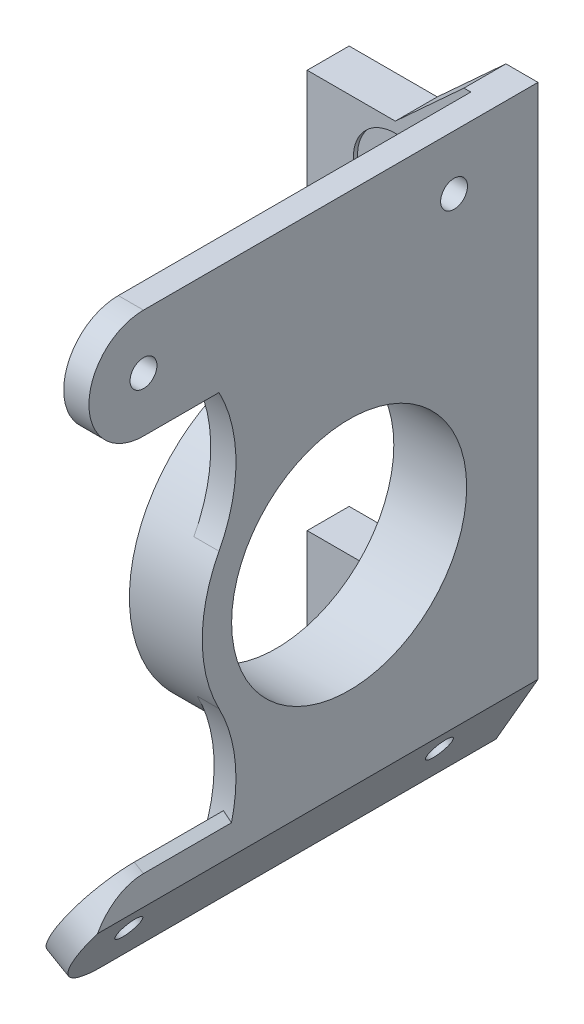
SolidWorks part; units mm, degrees
ref_plane "前视基准面" through (0, 0, 0) normal (0, 0, 1) x (1, 0, 0)
ref_plane "上视基准面" through (0, 0, 0) normal (0, 1, 0) x (1, 0, 0)
ref_plane "右视基准面" through (0, 0, 0) normal (1, 0, 0) x (0, 0, -1)
sketch "草图2" plane through (0, 0, 0) normal (0, 0, 1) x (1, 0, 0)
  line L0 (-14.7736, 24.3382) -> (-14.7736, -35.6618)
  line L1 (-14.7736, -35.6618) -> (30.2264, -35.6618)
  line L2 (7.7264, -35.6618) -> (7.7264, -23.1618)
  line L3 (21.55, -23.1618) -> (-6.0971, -23.1618)
  line L4 (-6.0971, -23.1618) -> (-6.0971, 11.8382)
  line L5 (-6.0971, 11.8382) -> (21.55, 11.8382)
  line L6 (7.7264, 11.8382) -> (7.7264, 24.3382)
  line L7 (30.2264, 24.3382) -> (-14.7736, 24.3382)
  line L8 (7.7264, 28.8603) -> (7.7264, -39.8897) construction
  line L9 (21.55, -23.1618) -> (21.55, 11.8382)
  line L10 (30.2264, 24.3382) -> (30.2264, -35.6618)
  line L11 (-18.1559, -5.6618) -> (33.2411, -5.6618) construction
  point P16 (-6.0971, -5.6618)
  point P17 (-14.7736, -5.6618)
  dimension "D1" = 45
  dimension "D2" = 35
  dimension "D3" = 60
extrude "凸台-拉伸2" add sketch "草图2" along normal blind 5 contours L6 L7 L0 L1 L2 L3 L4 L5 | L10 L7 L6 L5 L9 L3 L2 L1 region at (-3.5236, 23.6974, 0) region at (18.9764, 23.6974, 0)
sketch "草图4" plane through (0, 0, 5) normal (0, 0, 1) x (1, 0, 0)
  line L0 (-18.165, -5.6618) -> (33.9165, -5.6618) construction
  line L1 (-14.7736, 24.3382) -> (-14.7736, -35.6618) construction
  line L2 (-14.7736, -23.1618) -> (-6.0971, -23.1618)
  line L3 (-14.7736, -23.1618) -> (-14.7736, 11.8382)
  line L4 (-14.7736, 11.8382) -> (-6.0971, 11.8382)
  line L5 (-6.0971, -23.1618) -> (-6.0971, 11.8382)
  line L6 (-6.0971, -23.1618) -> (-6.0971, 11.8382) construction
  line L7 (7.7264, -39.813) -> (7.7264, 28.1228) construction
  line L8 (30.2264, 11.8382) -> (21.55, 11.8382)
  line L9 (21.55, -23.1618) -> (21.55, 11.8382)
  line L10 (30.2264, -23.1618) -> (21.55, -23.1618)
  line L11 (30.2264, -23.1618) -> (30.2264, 11.8382)
  point P17 (-14.7736, -5.6618)
  dimension "D1" = 35
extrude "凸台-拉伸15" add sketch "草图4" along normal blind 35
sketch "草图5" plane through (-14.7736, 0, 0) normal (-1, 0, 0) x (0, 0, 1)
  line L0 (0, -5.6618) -> (40, -5.6618)
  line L1 (0, 24.3382) -> (0, -35.6618) construction
  line L2 (40, 11.8382) -> (40, -23.1618) construction
  line L3 (22.5, 11.8382) -> (40, 11.8382)
  line L4 (40, 11.8382) -> (40, -23.1618)
  line L5 (40, -23.1618) -> (22.5, -23.1618)
  circle A0 centre (22.5, -5.6618) radius 17.5
  line M5 (5, -23.1618) -> (40, -23.1618)
  line M6 (40, -23.1618) -> (40, 11.8382)
  line M7 (40, 11.8382) -> (5, 11.8382)
  dimension "D1" = 35
extrude "切除-拉伸1" cut sketch "草图5" against normal blind 45 contours A0 M5 M6 | A0 M6 M7 region at (-14.7736, 7.9293, 36.0911) region at (-14.7736, -19.2528, 36.0911)
sketch "草图6" plane through (-14.7736, 0, 0) normal (-1, 0, 0) x (0, 0, 1)
  circle A0 centre (22.5, -5.6618) radius 14
  dimension "D1" = 28
extrude "切除-拉伸2" cut sketch "草图6" against normal blind 45
fillet "圆角1" radius 5 4 edges at (-6.0971, 11.8382, 2.5) (21.55, 11.8382, 2.5) (-6.0971, -23.1618, 2.5) (21.55, -23.1618, 2.5)
sketch "草图7" plane through (-6.0971, 0, 0) normal (1, 0, 0) x (0, 0, -1)
  circle A0 centre (-22.5, -5.6618) radius 15
  circle A1 centre (-22.5, -5.6618) radius 13
extrude "凸台-拉伸16" add sketch "草图7" against normal blind 1
sketch "草图8" plane through (21.55, 0, 0) normal (-1, 0, 0) x (0, 0, 1)
  circle A0 centre (22.5, -5.6618) radius 15
  circle A1 centre (22.5, -5.6618) radius 10
sketch "草图9" plane through (0, 0, 5) normal (0, 0, 1) x (1, 0, 0)
  line L0 (7.7264, 24.3382) -> (7.7264, -35.6618)
  line L13 (30.2264, 24.3382) -> (-14.7736, 24.3382) construction
  line L14 (-14.7736, -35.6618) -> (30.2264, -35.6618) construction
sketch "草图11" plane through (0, 0, 5) normal (0, 0, 1) x (1, 0, 0)
  line L0 (-14.7736, 18.0882) -> (30.2264, 18.0882)
  line L1 (-14.7736, 24.3382) -> (-14.7736, 11.8382) construction
  line L2 (30.2264, 24.3382) -> (30.2264, 11.8382) construction
  line L3 (7.7264, 24.3382) -> (7.7264, -35.6618) construction
  line L4 (30.2264, 24.3382) -> (-14.7736, 24.3382) construction
  line L5 (-14.7736, -35.6618) -> (30.2264, -35.6618) construction
  line L6 (7.7264, -5.6618) -> (45.6912, -5.6618) construction
  line L7 (45.6912, -5.6618) -> (45.6912, 4.9969) construction
  line L10 (-14.7736, -29.4118) -> (30.2264, -29.4118)
  line L11 (-14.7736, -23.1618) -> (-14.7736, -35.6618) construction
  point P4 (-2.7736, 18.0882)
  point P16 (-2.7736, -29.4118)
  point P18 (18.2264, -29.4118)
  point P25 (18.2264, 18.0882)
  dimension "D1" = 12
split "分割1" trim tools "草图9" bodies to split 111 resulting bodies 117 118
delete or keep bodies "实体-删除/保留 2" type delete bodies bodies 117
hole_wizard "打孔尺寸(%根据六角头螺)栓 全螺纹的类型1" positions "3D草图2" profile "草图31" counterbore size "M4" standard "GB"
sketch3d "3D草图2"
  point P0 (18.2264, 18.0882, 5)
  point P3 (18.2264, -29.4118, 5)
sketch "草图31" plane through (18.2264, 18.0882, 5) normal (1, 0, 0) x (0, -1, 0)
  line L0 (0, 0) -> (0, 6.2919)
  line L1 (0, 6.2919) -> (2.15, 5)
  line L2 (2.15, 5) -> (2.15, 0.5)
  line L3 (2.15, 0.5) -> (5, 0.5)
  line L4 (5, 0.5) -> (5, 0)
  line L5 (5, 0) -> (0, 0)
  line L10 (0, 6.2919) -> (-2.15, 5) construction
  line L11 (0, -6.35) -> (0, 107.95) construction
  dimension "孔直径" = 4.3
  dimension "孔深度" = 5
  dimension "柱形沉头孔直径" = 10
  dimension "柱形沉头孔深度" = 0.5
  dimension "导头角度" = 118
sketch "草图17" plane through (0, 0, 5) normal (0, 0, 1) x (1, 0, 0)
  line L5 (30.2264, 31.8382) -> (27.2264, 31.8382)
  line L6 (30.2264, 31.8382) -> (30.2264, 18.8382)
  line L7 (30.2264, 18.8382) -> (27.2264, 18.8382)
  line L8 (27.2264, 31.8382) -> (27.2264, 18.8382)
  line L9 (30.2264, 24.3382) -> (30.2264, 11.8382) construction
  line L10 (30.2264, 11.8382) -> (21.55, 11.8382) construction
  dimension "D1" = 3
  dimension "D4" = 13
  dimension "D6" = 7
extrude "凸台-拉伸20" add sketch "草图17" along normal blind 42
sketch "草图18" plane through (30.2264, 0, 0) normal (1, 0, 0) x (0, 0, -1)
  line L3 (-47, 18.8382) -> (-47, 31.8382)
  arc A0 (-47, 31.8382) -> (-47, 18.8382) centre (-47, 25.3382) ccw
extrude "凸台-拉伸21" add sketch "草图18" against normal blind 3
sketch "草图19" plane through (30.2264, 0, 0) normal (1, 0, 0) x (0, 0, -1)
  circle A0 centre (-47, 25.3382) radius 1.6
  circle A2 centre (-10, 25.3382) radius 1.6
  dimension "D1" = 37
extrude "切除-拉伸3" cut sketch "草图19" against normal blind 3
sketch "草图24" plane through (30.2264, 0, 0) normal (1, 0, 0) x (0, 0, -1)
  line L11 (-5, 18.8382) -> (-38, 18.8382)
  line L12 (-5, 18.8382) -> (-5, 11.8382)
  line L14 (-38, 18.8382) -> (-38, 2.4623) construction
  line L15 (-22.5, 11.8382) -> (-5, 11.8382) construction
  line L16 (-22.5, 11.8382) -> (-5, 11.8382)
  line L19 (-5, 11.8382) -> (-5, -23.1618) construction
  line L21 (-38, 2.4623) -> (-38, -13.7858) construction
  arc A2 (-22.5, 11.8382) -> (-22.5, -23.1618) centre (-22.5, -5.6618) ccw construction
  arc A3 (-22.5, 11.8382) -> (-38, 2.4623) centre (-22.5, -5.6618) ccw
  arc A4 (-38, 2.4623) -> (-38, -13.7858) centre (-22.5, -5.6618) ccw construction
  arc A6 (-38, 2.4623) -> (-38, 18.8382) centre (-53.622, 10.6503) ccw
  dimension "D1" = 33
extrude "凸台-拉伸25" add sketch "草图24" against normal blind 3
sketch "草图21" plane through (0, 0, 5) normal (0, 0, 1) x (1, 0, 0)
  line L1 (30.2264, 18.8382) -> (30.2264, 31.8382) construction
  line L5 (18.2264, 24.3382) -> (30.2264, 24.3382)
  line L6 (27.2264, 24.3382) -> (7.7264, 24.3382) construction
  line L8 (30.2264, 24.3382) -> (30.2264, 31.8382)
  line L9 (26.4082, 31.8382) -> (18.2264, 24.3382)
  line L15 (30.2264, 31.8382) -> (26.4082, 31.8382)
  line L16 (30.2264, 31.8382) -> (30.2264, 35.3382) construction
  line L17 (30.2264, 35.3382) -> (26.4082, 31.8382) construction
  dimension "D3" = 12
  dimension "D4" = 11
extrude "凸台-拉伸22" add sketch "草图21" against normal blind 5
sketch "草图34" plane through (0, 0, 5) normal (0, 0, 1) x (1, 0, 0)
  line L0 (30.2264, -23.1618) -> (30.2264, -35.6618) construction
  line L1 (22.6283, -36.9201) -> (25.2264, -38.4201)
  line L2 (22.6283, -36.9201) -> (29.1283, -25.6618)
  line L3 (29.1283, -25.6618) -> (30.2264, -26.2957)
  line L4 (25.2264, -38.4201) -> (30.2264, -29.7598)
  line L5 (22.6283, -36.9201) -> (31.7264, -27.1618) construction
  line L6 (29.1283, -25.6618) -> (25.2264, -38.4201) construction
  line L7 (21.55, -23.1618) -> (30.2264, -23.1618) construction
  line L8 (30.2264, -26.2957) -> (30.2264, -29.7598)
  line L9 (30.2264, -29.7598) -> (31.7264, -27.1618) construction
  line L10 (30.2264, -26.2957) -> (31.7264, -27.1618) construction
  point P0 (27.1774, -32.0409)
  dimension "D1" = 3
  dimension "D2" = 13
  dimension "D3" = 30
  dimension "D4" = 4
  dimension "D5" = 1.5
extrude "凸台-拉伸26" add sketch "草图34" along normal blind 42
sketch "草图37" plane through (30.2264, 0, 0) normal (1, 0, 0) x (0, 0, -1)
  line L0 (-40, -5.6618) -> (-5, -5.6618) construction
  line L1 (-5, 24.3382) -> (-5, -35.6618) construction
  line L3 (-37.7958, -29.7598) -> (-5, -29.7598)
  line L4 (-5, -29.7598) -> (-5, -23.1618)
  line L5 (-22.5, -23.1618) -> (-5, -23.1618) construction
  line L6 (-22.5, -23.1618) -> (-5, -23.1618)
  arc A0 (-38, 2.4623) -> (-22.5, -23.1618) centre (-22.5, -5.6618) ccw construction
  arc A1 (-38, 2.4623) -> (-38, 18.8382) centre (-53.622, 10.6503) ccw construction
  arc A2 (-38, 2.4623) -> (-38, 18.8382) centre (-53.622, 10.6503) ccw construction
  arc A3 (-38, -13.7858) -> (-37.7958, -29.7598) centre (-53.622, -21.9738) cw
  arc A5 (-38, -13.7858) -> (-22.5, -23.1618) centre (-22.5, -5.6618) ccw
  point P13 (-37.6293, -29.4118)
  point P15 (-37.7958, -29.7598)
  point P17 (0, 0)
extrude "凸台-拉伸27" add sketch "草图37" against normal blind 2.6
sketch "草图38" plane through (0, 0, 5) normal (0, 0, 1) x (1, 0, 0)
  line L3 (30.2264, -35.6618) -> (30.2264, -29.7598)
  line L4 (30.2264, -29.7598) -> (26.8189, -35.6618)
  line L5 (26.8189, -35.6618) -> (30.2264, -35.6618)
  line L6 (30.2264, -35.6618) -> (30.2264, -29.7598)
  line L7 (30.2264, -29.7598) -> (26.8189, -35.6618)
  line L8 (26.8189, -35.6618) -> (30.2264, -35.6618)
  dimension "D1" = 0
extrude "切除-拉伸5" cut sketch "草图38" against normal blind 22.6
sketch "草图39" plane through (0, 0, 5) normal (0, 0, 1) x (1, 0, 0)
  line L0 (22.6283, -36.9201) -> (20.4489, -35.6618)
  line L1 (7.7264, -35.6618) -> (23.3548, -35.6618) construction
  line L2 (20.4489, -35.6618) -> (23.3548, -35.6618)
  line L4 (26.8189, -35.6618) -> (23.3548, -35.6618)
  line L5 (25.2264, -38.4201) -> (26.8189, -35.6618)
  line L6 (22.6283, -36.9201) -> (25.2264, -38.4201)
  line L7 (23.3548, -35.6618) -> (22.6283, -36.9201)
  line L8 (26.8189, -35.6618) -> (23.3548, -35.6618)
  line L9 (25.2264, -38.4201) -> (26.8189, -35.6618)
  line L10 (22.6283, -36.9201) -> (25.2264, -38.4201)
  dimension "D1" = 0
extrude "凸台-拉伸28" add sketch "草图39" against normal up to surface (5 mm away) up to face at (20.3764, 18.0882, 0)
sketch "草图41" plane through (35.5562, -20.5284, 0) normal (0.866, -0.5, 0) x (0, 0, -1)
  line L1 (-47, -20.6596) -> (-47, -7.6596)
  line L2 (-47, -20.6596) -> (-47, -10.6596) construction
  line L3 (-47, -20.6596) -> (0, -20.6596) construction
  arc A0 (-47, -7.6596) -> (-47, -20.6596) centre (-47, -14.1596) ccw
  point P3 (-50.7971, -14.701)
  point P4 (-47, -7.6596)
  point P6 (-47, -20.6596)
  point P7 (0, 0)
  point P8 (0, 0)
  point P9 (-51.0727, -14.5453)
  point P10 (-51.0101, -14.5819)
  point P11 (-50.6815, -14.7621)
  point P13 (-47, -20.6596)
  point P16 (-51.3677, -14.362)
  point P17 (-47, -21.1591)
  point P20 (-48.9372, -14.1596)
  point P21 (0, 0)
  line M5 (-47, -10.6596) -> (-47, -20.6596)
extrude "凸台-拉伸29" add sketch "草图41" against normal up to surface (3 mm away) contours A0 M5 region at (28.4764, -32.7909, 49.7587) up to face at (26.4596, -30.2841, 29.578)
sketch "草图42" plane through (35.5562, -20.5284, 0) normal (0.866, -0.5, 0) x (0, 0, -1)
  line L0 (-47, -14.1596) -> (-10, -14.1596) construction
  circle A0 centre (-47, -14.1596) radius 1.5
  circle A1 centre (-10, -14.1596) radius 1.5
  point P6 (-10, -16.8581)
  point P7 (-10, -16.9611)
  dimension "D1" = 3
  dimension "D2" = 37
extrude "切除-拉伸6" cut sketch "草图42" against normal through all
sketch "草图44" plane through (0, 0, 47) normal (0, 0, -1) x (-1, 0, 0)
  line L3 (-31.7264, -27.1618) -> (-30.2264, -29.7598)
  line L4 (-30.2264, -29.7598) -> (-30.2264, -26.2957)
  line L5 (-30.2264, -26.2957) -> (-31.7264, -27.1618)
  line L6 (-31.7264, -27.1618) -> (-30.2264, -29.7598)
  line L7 (-30.2264, -29.7598) -> (-30.2264, -26.2957)
  line L8 (-30.2264, -26.2957) -> (-31.7264, -27.1618)
  dimension "D1" = 0
extrude "切除-拉伸7" cut sketch "草图44" against normal blind 8.6
move or copy body "实体-移动/复制2" [suppressed] bodies to move or copy 155
move or copy body "实体-移动/复制1" [suppressed] bodies to move or copy 146
